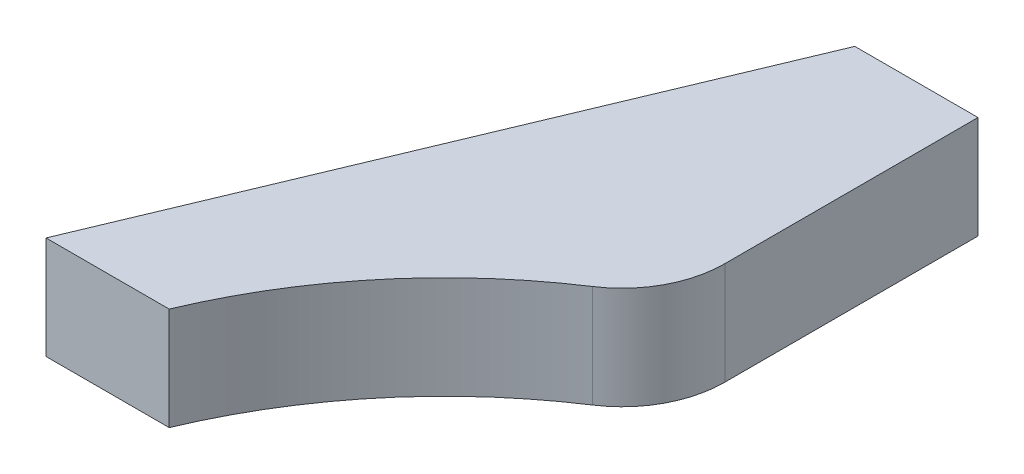
SolidWorks part; units mm, degrees
ref_plane "前视基准面" through (0, 0, 0) normal (0, 0, 1) x (1, 0, 0)
ref_plane "上视基准面" through (0, 0, 0) normal (0, 1, 0) x (1, 0, 0)
ref_plane "右视基准面" through (0, 0, 0) normal (1, 0, 0) x (0, 0, -1)
other "Configuration Table"
sketch "草图3" plane through (0, 0, 0) normal (0, 1, 0) x (1, 0, 0)
  line L0 (0, 0) -> (0, -9.9636) construction
  line L1 (-3, -3.3541) -> (3, -3.3541) construction
  line L2 (-3, -3.3541) -> (-3, -7.4162)
  line L3 (3, -3.3541) -> (3, -7.4162)
  line L7 (3, -7.4162) -> (3, -10.583)
  line L10 (-3, -43.8541) -> (3, -43.8541)
  line L11 (3, -43.8541) -> (3, -10.583)
  line L13 (-3, -7.4162) -> (-3, -43.8541)
  arc A0 (3, -3.3541) -> (-3, -3.3541) centre (0, 0) ccw
  point P6 (0, -3.3541)
  dimension "D1" = 9
  dimension "D2" = 6
  dimension "16.66" = 40.5
extrude "凸台-拉伸2" add sketch "草图3" along normal blind 5
sketch "草图4" plane through (0, 5, 0) normal (0, 1, 0) x (1, 0, 0)
  circle A0 centre (0, 0) radius 1.65
  dimension "D1" = 3.3
extrude "切除-拉伸1" cut sketch "草图4" against normal up to surface (5 mm away) up to face at (0, 0, 21.6406)
sketch "草图6" plane through (0, 5, 0) normal (0, 1, 0) x (1, 0, 0)
  line L0 (14.4495, -55.9701) -> (14.4495, -20.0301) construction
  line L1 (14.4495, -55.9701) -> (3, -43.8541) construction
  line L2 (3, -68.0861) -> (0.6636, -72.1328) construction
  line L3 (3, -43.8541) -> (-3, -43.8541) construction
  line L4 (3, -43.8541) -> (3, -33.746) construction
  line L5 (3, -43.8541) -> (3, -3.3541) construction
  line L6 (3, -33.746) -> (-3, -33.746)
  line L7 (-3, -3.3541) -> (-3, -43.8541) construction
  line L8 (14.4495, -55.9701) -> (1.9495, -77.6207) construction
  line L9 (1.9495, -77.6207) -> (0.7225, -79.746)
  arc A0 (3, -43.8541) -> (3, -68.0861) centre (14.4495, -55.9701) ccw construction
  arc A1 (-3, -43.8541) -> (0.6636, -72.1328) centre (14.4495, -55.9701) ccw construction
  arc A4 (3, -33.746) -> (1.9495, -77.6207) centre (14.4495, -55.9701) ccw
  arc A5 (-3, -33.746) -> (0.7225, -79.746) centre (8.4495, -55.9701) ccw
  dimension "D1" = 33.34
  dimension "D3" = 30
  dimension "D4" = 30
  dimension "D2" = 43.38
extrude "凸台-拉伸3" add sketch "草图6" against normal blind 5
sketch "草图7" plane through (0, 5, 0) normal (0, 1, 0) x (1, 0, 0)
  circle A0 centre (0, 0) radius 3
  dimension "D1" = 6
extrude "切除-拉伸2" cut sketch "草图7" against normal blind 3 from offset 4.5 offset against normal yes
sketch "草图8" plane through (0, 5, 0) normal (0, 1, 0) x (1, 0, 0)
  line L0 (-3, -38.0672) -> (-3, -43.8541)
  line L1 (-3, -43.8541) -> (3, -43.8541)
  line L2 (3, -43.8541) -> (3, -33.746)
  line L3 (3, -43.8541) -> (3, -3.3541) construction
  arc A0 (3, -33.746) -> (-3, -38.0672) centre (14.4495, -55.9701) ccw
extrude "切除-拉伸3" cut sketch "草图8" against normal blind 7.5
sketch "草图9" plane through (0, 5, 0) normal (0, 1, 0) x (1, 0, 0)
  line L0 (-3, -18.5501) -> (-14.615, -46.3249)
  line L1 (-3, -3.3541) -> (-3, -33.746) construction
  line L2 (-3, -18.5501) -> (-3, -33.746)
  arc A0 (-3, -33.746) -> (0.7225, -79.746) centre (8.4495, -55.9701) ccw construction
  arc A1 (-3, -33.746) -> (-14.615, -46.3249) centre (8.4495, -55.9701) ccw
extrude "凸台-拉伸4" add sketch "草图9" against normal blind 5
fillet "圆角1" radius 5 1 edges at (3, 2.5, 33.746)
fillet "圆角2" radius 5 1 edges at (1.9495, 2.5, 77.6207)
sketch "草图10" plane through (0, 5, 0) normal (0, 1, 0) x (1, 0, 0)
  line L0 (-3, -18.5501) -> (3, -18.5501)
  line L1 (-14.615, -46.3249) -> (-8.615, -46.3249)
  line L3 (3, -30.882) -> (3, -3.3541)
  line L4 (-3, -3.3541) -> (-3, -18.5501)
  line L5 (-3, -18.5501) -> (-14.615, -46.3249)
  line L6 (3, -30.882) -> (3, -3.3541)
  line L7 (-3, -3.3541) -> (-3, -18.5501)
  line L8 (-3, -18.5501) -> (-14.615, -46.3249)
  arc A5 (-14.615, -46.3249) -> (0.7225, -79.746) centre (8.4495, -55.9701) ccw
  arc A6 (0.7225, -79.746) -> (-1.1472, -75.5083) centre (-4.2666, -79.4159) ccw
  arc A7 (0.7416, -35.0633) -> (-1.1472, -75.5083) centre (14.4495, -55.9701) ccw
  arc A8 (0.7416, -35.0633) -> (3, -30.882) centre (-2, -30.882) ccw
  arc A9 (3, -3.3541) -> (-3, -3.3541) centre (0, 0) ccw
  arc A10 (-14.615, -46.3249) -> (0.7225, -79.746) centre (8.4495, -55.9701) ccw
  arc A11 (0.7225, -79.746) -> (-1.1472, -75.5083) centre (-4.2666, -79.4159) ccw
  arc A12 (0.7416, -35.0633) -> (-1.1472, -75.5083) centre (14.4495, -55.9701) ccw
  arc A13 (0.7416, -35.0633) -> (3, -30.882) centre (-2, -30.882) ccw
  arc A14 (3, -3.3541) -> (-3, -3.3541) centre (0, 0) ccw
  arc M9 (-14.615, -46.3249) -> (0.7225, -79.746) centre (8.4495, -55.9701) ccw
  arc M10 (0.7225, -79.746) -> (-1.1472, -75.5083) centre (-4.2666, -79.4159) ccw
  arc M11 (-1.1472, -75.5083) -> (0.7416, -35.0633) centre (14.4495, -55.9701) cw
  line M13 (3, -30.882) -> (3, -3.3541)
  arc M14 (3, -3.3541) -> (-3, -3.3541) centre (0, 0) ccw
  line M15 (-3, -3.3541) -> (-3, -18.5501)
  circle M17 centre (0, 0) radius 1.65
  dimension "D1" = 0
extrude "切除-拉伸4" cut sketch "草图10" against normal blind 5 contours L0 M15 M13 M14 M17 | L1 M9 M10 M11 region at (0, 5, 6.9285) region at (-10.6332, 5, 62.3411)
